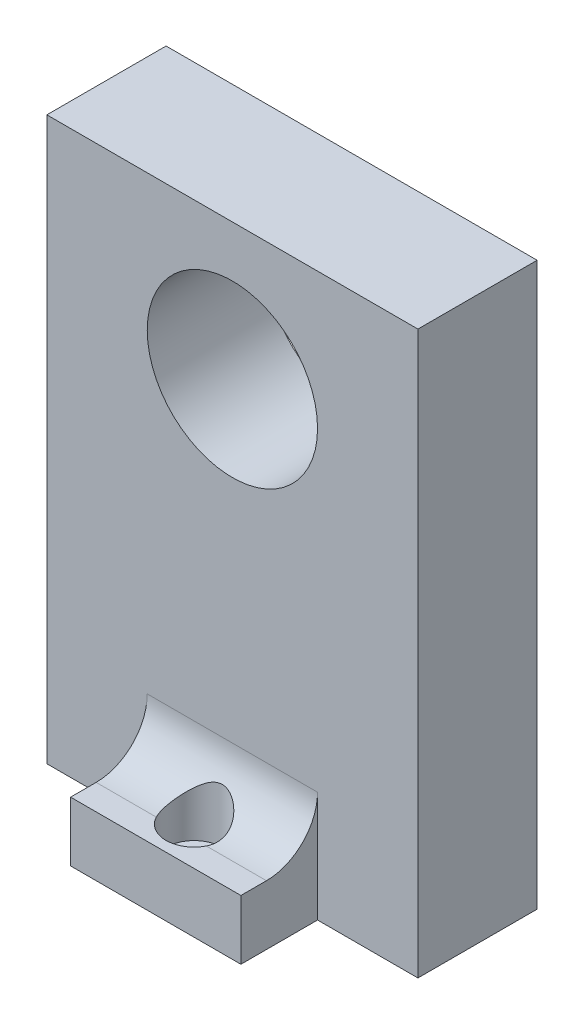
SolidWorks part; units mm, degrees
ref_plane "Front Plane" through (0, 0, 0) normal (0, 0, 1) x (1, 0, 0)
ref_plane "Top Plane" through (0, 0, 0) normal (0, 1, 0) x (1, 0, 0)
ref_plane "Right Plane" through (0, 0, 0) normal (1, 0, 0) x (0, 0, -1)
sketch "Sketch1" plane through (0, 0, 0) normal (0, 0, 1) x (1, 0, 0)
  line L1 (0, 0) -> (21.7877, 0)
  line L2 (0, 0) -> (0, 33)
  line L3 (0, 33) -> (21.7877, 33)
  line L4 (21.7877, 0) -> (21.7877, 33)
  dimension "D1" = 33
  dimension "D2" = 21.7877
extrude "Boss-Extrude1" add sketch "Sketch1" along normal blind 7
sketch "Sketch2" plane through (0, 0, 7) normal (0, 0, 1) x (1, 0, 0)
  line L0 (0, 0) -> (21.7877, 0) construction
  circle A0 centre (10.8939, 25) radius 5
  point P4 (10.8939, 0)
  point P5 (0, 0)
  dimension "D2" = 10
  dimension "D1" = 25
extrude "Cut-Extrude1" cut sketch "Sketch2" against normal through all
sketch "Sketch3" plane through (0, 0, 7) normal (0, 0, 1) x (1, 0, 0)
  line L0 (0, 0) -> (21.7877, 0) construction
  line L2 (15.8939, 0) -> (15.8939, 3.5)
  line L3 (15.8939, 3.5) -> (5.8939, 3.5)
  line L4 (5.8939, 0) -> (5.8939, 3.5)
  line L5 (10.8939, 0) -> (5.8939, 3.5) construction
  line L6 (15.8939, 3.5) -> (10.8939, 0) construction
  line L7 (5.8939, 0) -> (15.8939, 0)
  point P0 (10.8939, 0)
  dimension "D1" = 10
  dimension "D2" = 3.5
extrude "Boss-Extrude2" add sketch "Sketch3" along normal blind 4.5
ref_plane "Plane1" through (0, 0, 3.5) normal (0, 0, 1) x (1, 0, 0)
mirror "Mirror1" about plane through (0, 0, 3.5) normal (0, 0, 1) of "Boss-Extrude2"
sketch "Sketch4" plane through (0, 3.5, 0) normal (0, 1, 0) x (1, 0, 0)
  line L0 (5.8939, 4.5) -> (15.8939, 0) construction
  line L1 (15.8939, 4.5) -> (5.8939, 0) construction
  line L2 (5.8939, -11.5) -> (15.8939, -7) construction
  line L4 (24.7954, -12) -> (24.9898, -12) construction
  line L5 (24.9898, -12) -> (24.7954, -12) construction
  line L6 (15.8939, -11.5) -> (5.8939, -7) construction
  circle A0 centre (10.8939, 2.25) radius 1
  circle A1 centre (10.8939, -9.25) radius 1
  dimension "D1" = 2
extrude "Cut-Extrude2" cut sketch "Sketch4" against normal through all
sketch "Sketch5" plane through (0, 3.5, 0) normal (0, 1, 0) x (1, 0, 0)
  circle A0 centre (10.8939, 2.25) radius 1.65
  circle A1 centre (10.8939, -9.25) radius 1.65
  dimension "D1" = 3.3
extrude "Cut-Extrude3" cut sketch "Sketch5" against normal blind 2
fillet "Fillet1" radius 3 2 edges at (10.8939, 3.5, 7) (10.8939, 3.5, 0)
